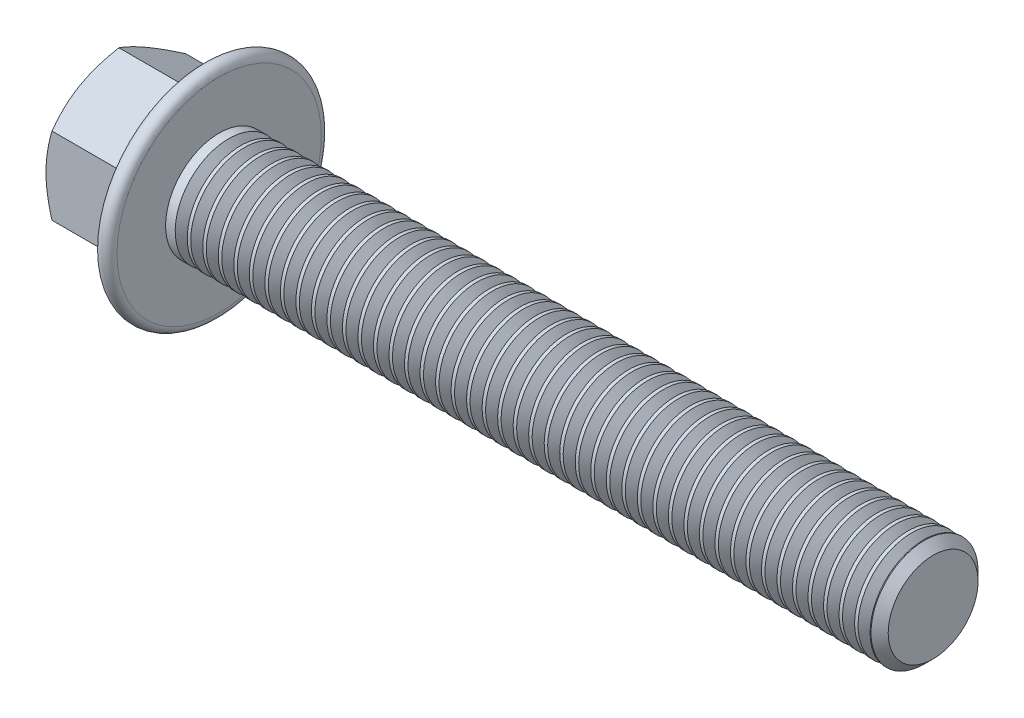
SolidWorks part; units mm, degrees
extrude "BaseHead" add sketch "Sketch1" along normal blind 11.9
sketch "Sketch1" plane through (0, 0, 0) normal (1, 0, 0) x (0, 0, -1)
  line L0 (7.5, 4.3301) -> (7.5, -4.3301)
  line L1 (-7.5, 4.3301) -> (-7.5, -4.3301)
  line L2 (7.5, -4.3301) -> (0, -8.6603)
  line L3 (0, -8.6603) -> (-7.5, -4.3301)
  line L4 (7.5, 4.3301) -> (0, 8.6603)
  line L5 (0, 8.6603) -> (-7.5, 4.3301)
  dimension "D2" = 120
  dimension "D3" = 7.5
  dimension "D4" = 7.5
  dimension "D5" = 7.5
ref_plane "Plane1" through (0, 0, 0) normal (0, 0, 1) x (1, 0, 0)
ref_plane "Plane2" through (0, 0, 0) normal (0, 1, 0) x (1, 0, 0)
ref_plane "Plane3" through (0, 0, 0) normal (1, 0, 0) x (0, 0, -1)
sketch "BodySke" plane through (0, 0, 0) normal (0, 0, 1) x (1, 0, 0)
  line L0 (0, 4.3301) -> (0, -4.3301) construction
  line L1 (0, 0) -> (91.9, 0)
  line L2 (0, 0) -> (0, 6)
  line L3 (0, 6) -> (90.936, 6)
  line L4 (91.9, 0) -> (91.9, 5.036)
  line L5 (11.9, 8.6603) -> (11.9, 4.3301) construction
  line L6 (91.9, 5.036) -> (90.936, 6)
  line L7 (0, 0) -> (96.52, 0) construction
  line L8 (91.9, -5.036) -> (90.936, -6) construction
  line L9 (0, -6) -> (90.936, -6) construction
  line L10 (13.65, 15.24) -> (13.65, -1.27) construction
  line L11 (-28.1, 15.24) -> (-28.1, -1.27) construction
  line L12 (11.9, 4.3301) -> (11.9, -4.3301) construction
  dimension "Diameter" = 12
revolve "BaseBody" add sketch "BodySke"
cosmetic thread "ThreadCosmetic" [suppressed]
fillet "HeadFillet" [suppressed] radius 0.6
sketch "Sketch3" plane through (0, 0, 0) normal (0, 0, 1) x (1, 0, 0)
  line L0 (0, 7.5) -> (3.5566, 13.6603)
  line L1 (0, 8.6603) -> (0, 4.3301) construction
  line L2 (3.5566, 13.6603) -> (3.5566, 18.6603)
  line L3 (3.5566, 18.6603) -> (-10, 18.6603)
  line L4 (-10, 18.6603) -> (-10, 7.5)
  line L5 (-10, 7.5) -> (0, 7.5)
  line L6 (0, 0) -> (99.06, 0) construction
  line L7 (11.9, 8.6603) -> (0, 8.6603) construction
  dimension "D1" = 7.5
  dimension "D2" = 5
  dimension "D3" = 10
  dimension "D4" = 5
  dimension "Head_ch_ang" = 30
revolve "HeadChamfer" cut sketch "Sketch3" angle 360 about L6
sketch "Sketch4" plane through (0, 0, 0) normal (0, 0, 1) x (1, 0, 0)
  line L0 (5.8748, 0) -> (10.1543, 11.7578)
  line L1 (11.9, 8.6603) -> (11.9, 4.3301) construction
  line L2 (10.1, 34.3444) -> (10.1, 16.9779) construction
  line L3 (11.9, 0) -> (11.9, 11.45)
  line L4 (8.3021, 12.35) -> (20.1618, 12.35) construction
  line L5 (0, 0) -> (95.25, 0) construction
  line L6 (0, 0) -> (96.52, 0) construction
  line L7 (5.8748, 0) -> (11.9, 0)
  line L8 (8.3021, -12.35) -> (20.1618, -12.35) construction
  arc A0 (11.9, 11.45) -> (10.1543, 11.7578) centre (11, 11.45) ccw
  dimension "D1" = 20
  dimension "Flange_thickness" = 1.8
  dimension "Flange_dia" = 24.7
revolve "Flange" add sketch "Sketch4" angle 360 about L5
fillet "FlangeHexFillet" radius 0.24 6 edges
sketch "ThdSchSke" plane through (0, 0, 0) normal (0, 0, 1) x (1, 0, 0)
  line L0 (13.65, -5.036) -> (12.975, -6)
  line L1 (13.65, -5.036) -> (14.325, -6)
  line L2 (14.325, -6) -> (14.325, -7.5)
  line L3 (-3.175, 0) -> (5.1513, 0) construction
  line L5 (14.325, -7.5) -> (12.975, -7.5)
  line L6 (12.975, -7.5) -> (12.975, -6)
  dimension "Thread_minor" = 10.072
  dimension "Diameter" = 12
  dimension "Start" = 13.65
revolve "ThreadSchematic" cut sketch "ThdSchSke" angle 360 about L3
pattern_linear "ThdSchPat" count 45 spacing 1.7389 along (1, 0, 0) of "ThreadSchematic"
equation "\"D3@Sketch1\" = \"Width_flats@Sketch1\" / 2"
equation "\"D4@Sketch1\" = \"D3@Sketch1\""
equation "\"D5@Sketch1\" = \"D4@Sketch1\""
equation "\"Thread_minor@ThreadCosmetic\" = \"Minor_dia@BodySke\""
equation "\"D1@Sketch3\" = \"Width_flats@Sketch1\" / 2"
equation "\"Thread_length@ThreadCosmetic\" = ((sgn( (\"Length@BodySke\" - \"Advance@BodySke\" ) - \"Thread_nom@BodySke\" )-1)*( (\"Length@BodySke\" - \"Advance@BodySke\" ) - \"Thread_nom@BodySke\" ))/-2+ \"Thread_nom@BodySke\""
equation "\"Thread_minor@ThdSchSke\" = \"Minor_dia@BodySke\""
equation "\"Diameter@ThdSchSke\" = \"Diameter@BodySke\""
equation "\"Overcut@ThdSchSke\" = \"Diameter@BodySke\" * 1.25"
equation "\"Start@ThdSchSke\" = \"Head_ht@BaseHead\" + \"Length@BodySke\" - \"Thread_length@ThreadCosmetic\"  '---Non-countersunk---"
equation "\"Num_threads@ThdSchPat\" = int( \"Thread_length@ThreadCosmetic\" / \"Advance@BodySke\" + 0.999 )  + 1"
equation "\"Advance@ThdSchPat\" = \"Thread_length@ThreadCosmetic\" /  (\"Num_threads@ThdSchPat\" - 1) 'relax it"
equation "\"Num_threads@ThdSchPat\" = \"Num_threads@ThdSchPat\" - sgn( \"Num_threads@ThdSchPat\" - 1) '---chamfered tips only---"
